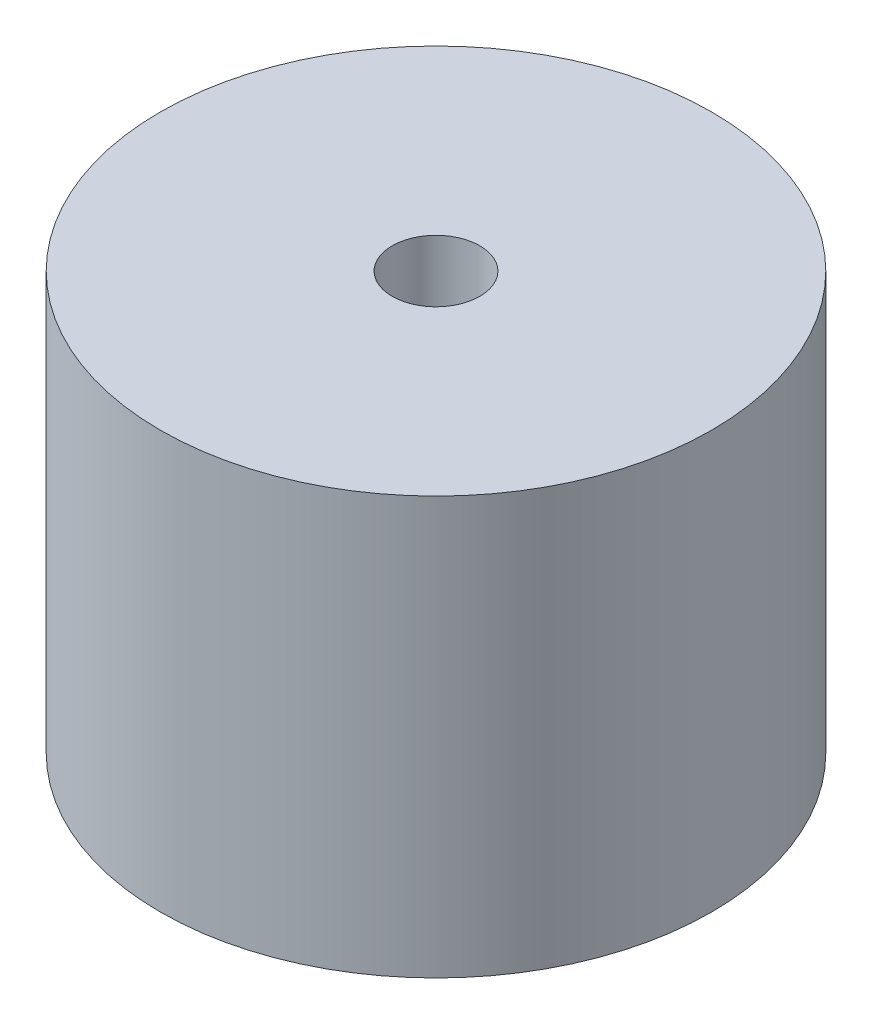
SolidWorks part; units mm, degrees
ref_plane "Front Plane" through (0, 0, 0) normal (0, 0, 1) x (1, 0, 0)
ref_plane "Top Plane" through (0, 0, 0) normal (0, 1, 0) x (1, 0, 0)
ref_plane "Right Plane" through (0, 0, 0) normal (1, 0, 0) x (0, 0, -1)
sketch "Sketch1" plane through (0, 0, 0) normal (0, 1, 0) x (1, 0, 0)
  circle A0 centre (0, 0) radius 2.1
  circle A1 centre (0, 0) radius 13.21
  dimension "D1" = 4.2
  dimension "D2" = 13.21
extrude "Boss-Extrude1" add sketch "Sketch1" along normal blind 20
sketch "Sketch2" plane through (0, 0, 0) normal (1, 0, 0) x (0, 0, -1)
  line L0 (-13.21, 0) -> (-13.21, -12.4903)
  line L1 (-13.21, -12.4903) -> (-4.21, -12.4903)
  line L2 (-4.21, -12.4903) -> (-4.21, 0)
  line L3 (-4.21, 0) -> (-13.21, 0)
  line L4 (-13.21, 0) -> (13.21, 0) construction
  circle A0 centre (-10.21, -8.4903) radius 1.2 construction
  dimension "D1" = 4
  dimension "D2" = 9
